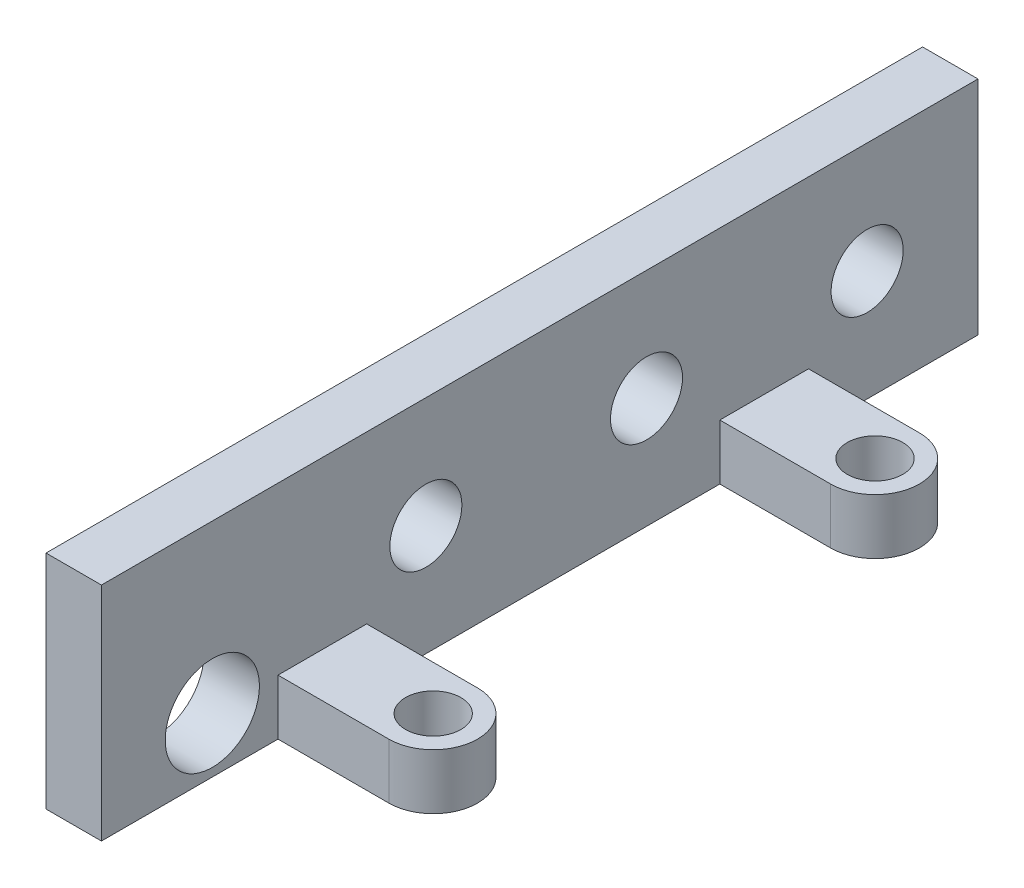
SolidWorks part; units mm, degrees
ref_plane "Front Plane" through (0, 0, 0) normal (0, 0, 1) x (1, 0, 0)
ref_plane "Top Plane" through (0, 0, 0) normal (0, 1, 0) x (1, 0, 0)
ref_plane "Right Plane" through (0, 0, 0) normal (1, 0, 0) x (0, 0, -1)
sketch "Sketch1" plane through (0, 0, 0) normal (1, 0, 0) x (0, 0, -1)
  line L1 (0, 0) -> (-79.0616, 0)
  line L2 (0, 0) -> (0, 20)
  line L3 (0, 20) -> (-79.0616, 20)
  line L4 (-79.0616, 0) -> (-79.0616, 20)
  circle A0 centre (-29.9, 10) radius 3.25
  circle A1 centre (-49.8, 10) radius 3.25
  circle A2 centre (-69.0616, 5) radius 4.25
  circle A3 centre (-10, 10) radius 3.25
  dimension "D1" = 10
  dimension "D3" = 6.5
  dimension "D4" = 10
  dimension "D10" = 8.5
  dimension "D2" = 20
  dimension "D5" = 19.9
  dimension "D6" = 19.9
  dimension "D7" = 10
  dimension "D8" = 5
  dimension "D9" = 19.9
extrude "Boss-Extrude1" add sketch "Sketch1" along normal blind 5
sketch "Sketch2" plane through (5, 0, 0) normal (1, 0, 0) x (0, 0, -1)
  line L0 (-79.0616, 0) -> (-39.2116, 0)
  line L2 (-79.0616, 0) -> (0, 0) construction
  line L3 (0, 20) -> (-79.0616, 20) construction
  line L4 (-15.2866, 5) -> (-23.2866, 5)
  line L5 (-15.2866, 0) -> (-15.2866, 5)
  line L6 (-63.1366, 0) -> (-55.1366, 0)
  line L7 (-63.1366, 0) -> (-63.1366, 5)
  line L8 (-63.1366, 5) -> (-55.1366, 5)
  line L9 (-55.1366, 5) -> (-55.1366, 0)
  line L10 (-39.2116, 0) -> (-39.2116, 20) construction
  line L13 (-15.2866, 0) -> (-23.2866, 0)
  line L14 (-23.2866, 5) -> (-23.2866, 0)
  point P2 (-59.1366, 0)
  point P5 (-59.1366, 0)
  dimension "D1" = 39.85
  dimension "D5" = 8
  dimension "D6" = 5
extrude "Boss-Extrude2" add sketch "Sketch2" along normal blind 10 contours L9 L6 L7 L8 | L4 L14 L13 L5
sketch "Sketch3" plane through (0, 5, 0) normal (0, 1, 0) x (1, 0, 0)
  line L0 (15, -55.1366) -> (15, -63.1366)
  arc A0 (15, -55.1366) -> (15, -63.1366) centre (15, -59.1366) cw
  circle A1 centre (15, -59.1366) radius 2.5
  dimension "D1" = 5
extrude "Boss-Extrude3" add sketch "Sketch3" against normal blind 5 contours A0 L0
extrude "Cut-Extrude2" cut sketch "Sketch3<6>" against normal through all contours A1
sketch "Sketch3<6>" plane through (0, 5, 0) normal (0, 1, 0) x (1, 0, 0) same geometry as "Sketch3"
ref_plane "Plane1" through (0, 0, 39.2116) normal (0, 0, 1) x (1, 0, 0)
mirror "Mirror1" about plane through (0, 0, 39.2116) normal (0, 0, 1) of "Boss-Extrude3", "Cut-Extrude2"
